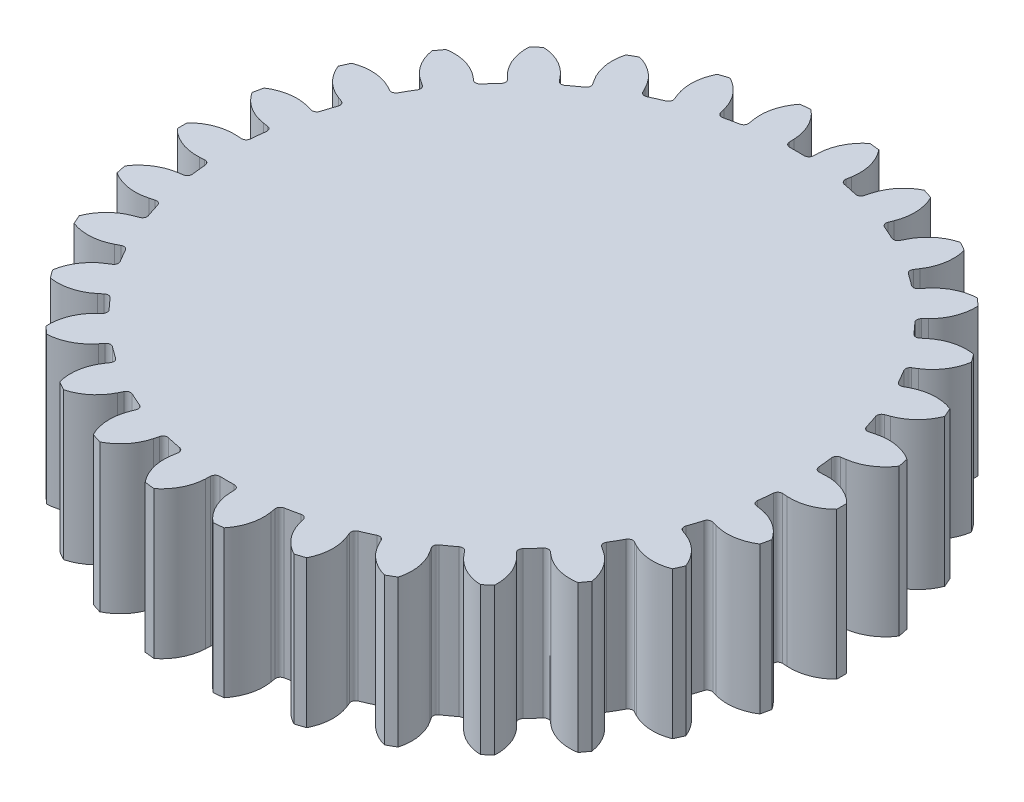
SolidWorks part; units mm, degrees
material "1023 Carbon Steel Sheet (SS)"
ref_plane "Front Plane" through (0, 0, 0) normal (0, 0, 1) x (1, 0, 0)
ref_plane "Top Plane" through (0, 0, 0) normal (0, 1, 0) x (1, 0, 0)
ref_plane "Right Plane" through (0, 0, 0) normal (1, 0, 0) x (0, 0, -1)
sketch "Sketch1" plane through (0, 0, 0) normal (0, 1, 0) x (1, 0, 0)
  circle A0 centre (0, 0) radius 7.112
  dimension "D1" = 14.224
extrude "Boss-Extrude1" add sketch "Sketch1" along normal blind 3.175
ref_axis "Axis1" through (0, 3.175, 0) along (0, -1, 0)
sketch "Sketch8" plane through (0, 3.175, 0) normal (0, 1, 0) x (1, 0, 0)
  line L0 (0, 0) -> (0, 7.112) construction
  line L1 (0, 0) -> (-0.2939, 7.1059) construction
  line L2 (-0.2624, 6.3446) -> (-0.254, 6.1415)
  line L3 (0.2624, 6.3446) -> (0.254, 6.1415)
  circle A0 centre (0, 0) radius 7.112 construction
  arc A1 (0.635, 7.0836) -> (-0.635, 7.0836) centre (0, 0) ccw
  arc A2 (-0.254, 6.1415) -> (0.254, 6.1415) centre (0, 0) cw
  arc A3 (-0.635, 7.0836) -> (-0.2624, 6.3446) centre (-1.2637, 6.3032) cw
  arc A4 (0.635, 7.0836) -> (0.2624, 6.3446) centre (1.2637, 6.3032) ccw
  dimension "D1" = 0.254
  dimension "D2" = 0.762
  dimension "D3" = 0.2032
  dimension "D4" = 1.27
extrude "Cut-Extrude3" cut sketch "Sketch8" against normal through all
fillet "Fillet1" radius 0.1016 2 edges at (0.254, 1.5875, -6.1415) (-0.254, 1.5875, -6.1415)
pattern_circular "CirPattern3" count 30 over 360 about axis through (0, 3.175, 0) along (0, -1, 0) of "Cut-Extrude3", "Fillet1"
sketch "Sketch5" plane through (0, 0, 0) normal (0, -1, 0) x (1, 0, 0)
  line L1 (-1.905, -1.905) -> (1.905, -1.905)
  line L2 (-1.905, -1.905) -> (-1.905, 1.905)
  line L3 (-1.905, 1.905) -> (1.905, 1.905)
  line L4 (1.905, -1.905) -> (1.905, 1.905)
  line L5 (-1.905, -1.905) -> (1.905, 1.905) construction
  line L6 (-1.905, 1.905) -> (1.905, -1.905) construction
  point P0 (0, 0)
  dimension "D1" = 3.81
extrude "Cut-Extrude2" cut sketch "Sketch5" against normal blind 1.27
